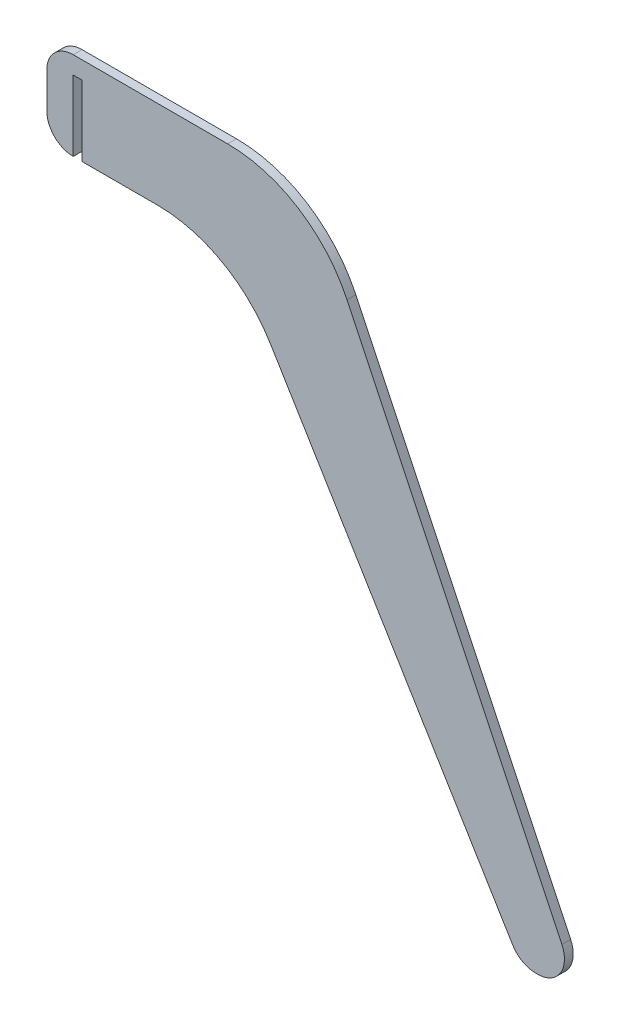
SolidWorks part; units mm, degrees
ref_plane "Front Plane" through (0, 0, 0) normal (0, 0, 1) x (1, 0, 0)
ref_plane "Top Plane" through (0, 0, 0) normal (0, 1, 0) x (1, 0, 0)
ref_plane "Right Plane" through (0, 0, 0) normal (1, 0, 0) x (0, 0, -1)
sketch "Sketch2" plane through (0, 0, 0) normal (0, 0, 1) x (1, 0, 0)
  line L10 (0, 0) -> (0, 1)
  line L15 (0, 1) -> (3, 1)
  line L16 (3, 1) -> (6.0495, -5.4009)
  line L17 (6.0495, -5.4009) -> (5.3754, -5.4009)
  line L18 (5.3754, -5.4009) -> (2.1, 0)
  line L20 (0, 0) -> (0.3, 0)
  line L21 (0.3, 0) -> (0.3, 0.8)
  line L22 (0.3, 0.8) -> (0.4, 0.8)
  line L23 (0.4, 0.8) -> (0.4, 0)
  line L24 (0.4, 0) -> (2.1, 0)
  point P2 (6.0495, -5.4009)
  dimension "D1" = 3
  dimension "D2" = 0.3
  dimension "D3" = 1
  dimension "D4" = 0.1
  dimension "D5" = 2.1
  dimension "D6" = 0.8
extrude "Boss-Extrude1" add sketch "Sketch2" along normal blind 0.1
fillet "Fillet1" radius 1.5 2 edges at (3, 1, 0.05) (2.1, 0, 0.05)
fillet "Fillet2" radius 0.3 4 edges at (6.0495, -5.4009, 0.05) (5.3754, -5.4009, 0.05) (0, 1, 0.05) (0, 0, 0.05)
